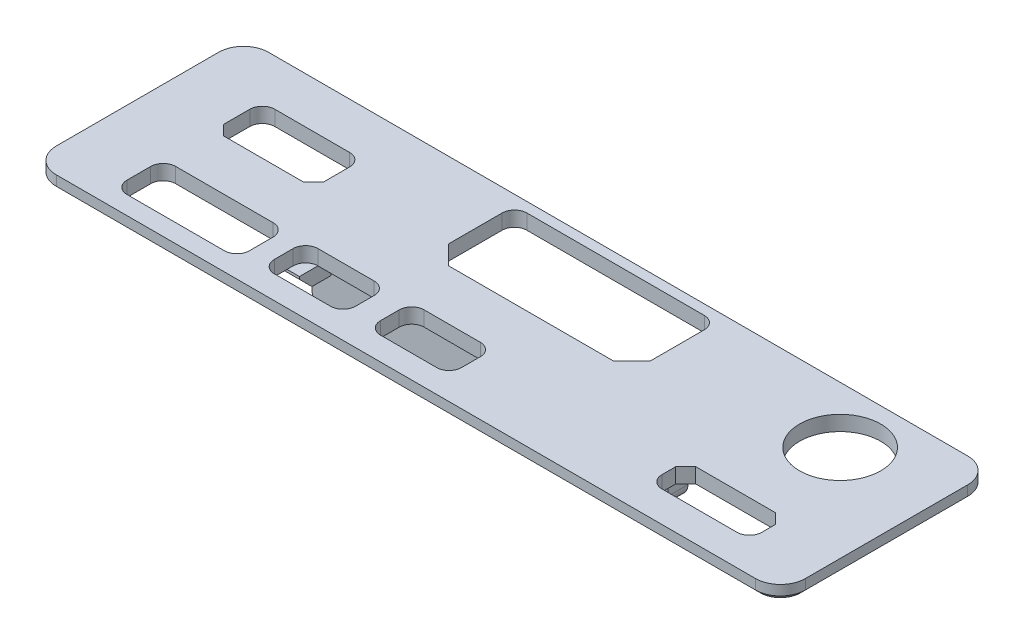
SolidWorks part; units mm, degrees
ref_plane "前视基准面" through (0, 0, 0) normal (0, 0, 1) x (1, 0, 0)
ref_plane "上视基准面" through (0, 0, 0) normal (0, 1, 0) x (1, 0, 0)
ref_plane "右视基准面" through (0, 0, 0) normal (1, 0, 0) x (0, 0, -1)
sketch "草图1" plane through (0, 0, 0) normal (0, 1, 0) x (1, 0, 0)
  line L1 (-30, 8.5) -> (30, 8.5)
  line L2 (-30, 8.5) -> (-30, -8.5)
  line L3 (-30, -8.5) -> (30, -8.5)
  line L4 (30, 8.5) -> (30, -8.5)
  line L5 (-30, 8.5) -> (30, -8.5) construction
  line L6 (-30, -8.5) -> (30, 8.5) construction
  point P0 (0, 0)
  dimension "D1" = 60
  dimension "D2" = 17
extrude "凸台-拉伸1" add sketch "草图1" along normal blind 1.2
sketch "草图4" plane through (0, 1.2, 0) normal (0, 1, 0) x (1, 0, 0)
  line L0 (-30, 8.5) -> (-30, -8.5) construction
  line L1 (-24.8, 4.8) -> (-16.8, 4.8)
  line L2 (-24.8, 4.8) -> (-24.8, 0.9)
  line L3 (-24.8, 0.9) -> (-16.8, 0.9)
  line L4 (-16.8, 4.8) -> (-16.8, 0.9)
  line L5 (-7.5, 7.7) -> (8.7, 7.7)
  line L6 (-7.5, 7.7) -> (-7.5, 0.9)
  line L7 (-7.5, 0.9) -> (8.7, 0.9)
  line L8 (8.7, 7.7) -> (8.7, 0.9)
  line L13 (17.05, -3.1348) -> (25.05, -3.1348)
  line L14 (17.05, -3.1348) -> (17.05, -6.0348)
  line L15 (17.05, -6.0348) -> (25.05, -6.0348)
  line L16 (25.05, -3.1348) -> (25.05, -6.0348)
  line L17 (-4.9, -3.1348) -> (1.6, -3.1348)
  line L18 (-4.9, -3.1348) -> (-4.9, -6.6348)
  line L19 (-4.9, -6.6348) -> (1.6, -6.6348)
  line L20 (1.6, -3.1348) -> (1.6, -6.6348)
  line L21 (-13.4, -3.1348) -> (-6.9, -3.1348)
  line L22 (-13.4, -3.1348) -> (-13.4, -6.6348)
  line L23 (-13.4, -6.6348) -> (-6.9, -6.6348)
  line L24 (-6.9, -3.1348) -> (-6.9, -6.6348)
  line L25 (-24.8, -3.1348) -> (-15, -3.1348)
  line L26 (-24.8, -3.1348) -> (-24.8, -7.0348)
  line L27 (-24.8, -7.0348) -> (-15, -7.0348)
  line L28 (-15, -3.1348) -> (-15, -7.0348)
  line L29 (30, 8.5) -> (-30, 8.5) construction
  line L31 (30, -8.5) -> (30, 8.5) construction
  line L32 (30, 8.5) -> (-30, 8.5) construction
  circle A0 centre (22.2985, 3.9832) radius 3.25
  dimension "D21" = 6.5
  dimension "D1" = 3.5
  dimension "D2" = 6.5
  dimension "D3" = 6.5
  dimension "D4" = 3.5
  dimension "D5" = 8
  dimension "D6" = 3.9
  dimension "D7" = 16.2
  dimension "D8" = 8
  dimension "D9" = 2.9
  dimension "D10" = 5.2
  dimension "D11" = 7.6
  dimension "D12" = 11.6348
  dimension "D13" = 16.6
  dimension "D14" = 25.1
  dimension "D15" = 4.95
  dimension "D16" = 9.8
  dimension "D17" = 22.5
  dimension "D19" = 7.7015
  dimension "D20" = 4.5168
  dimension "D22" = 6.8
extrude "切除-拉伸1" cut sketch "草图4" against normal up to next
fillet "圆角2" radius 1 18 edges at (-24.8, 0.6, -4.8) (-16.8, 0.6, -4.8) (8.7, 0.6, -7.7) (-7.5, 0.6, -7.7) (25.05, 0.6, 6.0348) (17.05, 0.6, 6.0348) (1.6, 0.6, 6.6348) (1.6, 0.6, 3.1348) (-4.9, 0.6, 3.1348) (-4.9, 0.6, 6.6348) (-6.9, 0.6, 6.6348) (-6.9, 0.6, 3.1348) (-13.4, 0.6, 3.1348) (-13.4, 0.6, 6.6348) (-15, 0.6, 7.0348) (-15, 0.6, 3.1348) (-24.8, 0.6, 3.1348) (-24.8, 0.6, 7.0348)
chamfer "倒角1" distance 0.8 angle 45 4 edges at (17.05, 0.6, 3.1348) (25.05, 0.6, 3.1348) (-16.8, 0.6, -0.9) (-24.8, 0.6, -0.9)
sketch "草图5" plane through (0, 0, 0) normal (0, -1, 0) x (1, 0, 0)
  line L0 (-30, -8.5) -> (-30, 8.5) construction
  line L1 (-13.9089, -3.3832) -> (-12.4089, -3.3832)
  line L2 (-13.9089, -3.3832) -> (-13.9089, 4.6168)
  line L3 (-13.9089, 4.6168) -> (-12.4089, 4.6168)
  line L4 (-12.4089, -3.3832) -> (-12.4089, 4.6168)
  line L5 (13.0911, -3.3832) -> (14.5911, -3.3832)
  line L6 (13.0911, -3.3832) -> (13.0911, 4.6168)
  line L7 (13.0911, 4.6168) -> (14.5911, 4.6168)
  line L8 (14.5911, -3.3832) -> (14.5911, 4.6168)
  line L9 (30, -8.5) -> (-30, -8.5) construction
  line L10 (30, 8.5) -> (30, -8.5) construction
  dimension "D1" = 1.5
  dimension "D2" = 8
  dimension "D3" = 1.5
  dimension "D4" = 8
  dimension "D5" = 16.0911
  dimension "D6" = 5.1168
  dimension "D7" = 5.1168
  dimension "D8" = 15.4089
extrude "凸台-拉伸2" add sketch "草图5" along normal blind 1.2
sketch "草图6" plane through (0, 0, 0) normal (0, -1, 0) x (1, 0, 0)
  line L0 (-13.9089, 4.6168) -> (-13.9089, -3.3832) construction
  line L1 (-13.9089, 2.1) -> (14.5911, 2.1)
  line L2 (-13.9089, 2.1) -> (-13.9089, 0.5)
  line L3 (-13.9089, 0.5) -> (14.5911, 0.5)
  line L4 (14.5911, 2.1) -> (14.5911, 0.5)
  line L5 (30, -8.5) -> (-30, -8.5) construction
  dimension "D1" = 1.6
  dimension "D2" = 9
extrude "凸台-拉伸3" add sketch "草图6" along normal blind 4
fillet "圆角3" radius 1 2 edges at (14.5911, -4, 1.3) (-13.9089, -4, 1.3)
chamfer "倒角2" distance 1 angle 45 4 edges at (13.8411, -1.2, -3.3832) (-13.1589, -1.2, -3.3832) (13.8411, -1.2, 4.6168) (-13.1589, -1.2, 4.6168)
fillet "圆角4" radius 2 4 edges at (30, 0.6, 8.5) (30, 0.6, -8.5) (-30, 0.6, 8.5) (-30, 0.6, -8.5)
chamfer "倒角5" distance 0.4 angle 45 8 edges at (0, 0, -8.5) (-29.4142, 0, -7.9142) (29.4142, 0, -7.9142) (-30, 0, 0) (30, 0, 0) (-29.4142, 0, 7.9142) (29.4142, 0, 7.9142) (0, 0, 8.5)
chamfer "倒角6" distance 1.5 angle 45 2 edges at (8.7, 0.6, -0.9) (-7.5, 0.6, -0.9)
